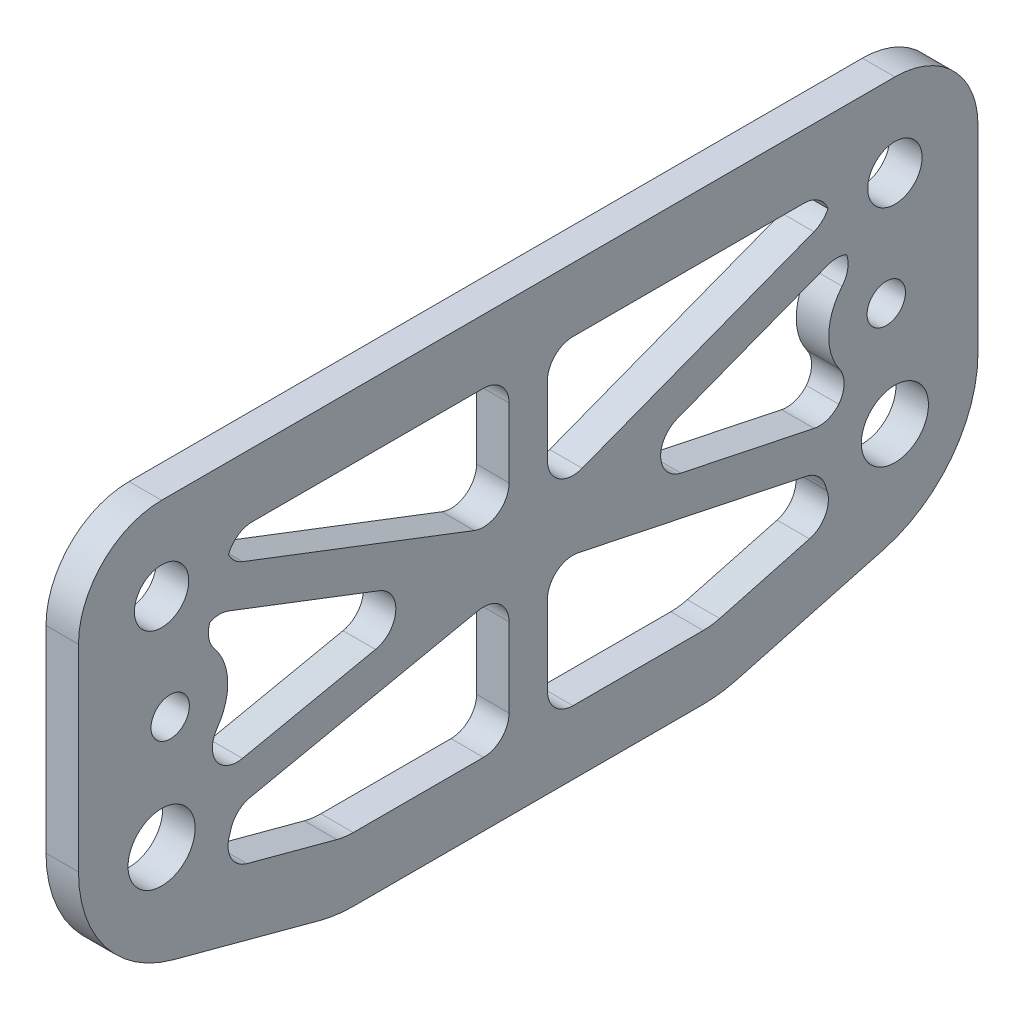
SolidWorks part; units mm, degrees
ref_plane "Front Plane" through (0, 0, 0) normal (0, 0, 1) x (1, 0, 0)
ref_plane "Top Plane" through (0, 0, 0) normal (0, 1, 0) x (1, 0, 0)
ref_plane "Right Plane" through (0, 0, 0) normal (1, 0, 0) x (0, 0, -1)
sketch "Sketch1" plane through (0, 0, 0) normal (1, 0, 0) x (0, 0, -1)
  line L0 (15, 17.5) -> (28.675, 17.5)
  line L1 (-15, -17.5) -> (15, -17.5)
  line L3 (-15, 17.5) -> (15, 17.5)
  line L5 (-15, -17.5) -> (15, 17.5) construction
  line L6 (-15, 17.5) -> (15, -17.5) construction
  line L8 (0, 17.5) -> (0, -17.5) construction
  line L10 (-15, 17.5) -> (-28.675, 17.5)
  line L11 (23.175, 120.4881) -> (23.175, -106.9119) construction
  line L13 (35.175, 11) -> (35.175, -4.4209)
  line L14 (27.7632, -14.0801) -> (15, -17.5)
  line L16 (-35.175, 11) -> (-35.175, -4.4209)
  line L17 (-27.7632, -14.0801) -> (-15, -17.5)
  arc A0 (28.675, 17.5) -> (35.175, 11) centre (28.675, 11) cw
  circle A1 centre (28.675, 11) radius 5.5 construction
  circle A2 centre (-28.675, 11) radius 5.5 construction
  arc A3 (-28.675, 17.5) -> (-35.175, 11) centre (-28.675, 11) ccw
  arc A4 (35.175, -4.4209) -> (27.7632, -14.0801) centre (25.175, -4.4209) cw
  circle A5 centre (28.675, 11) radius 2.125
  arc A6 (-35.175, -4.4209) -> (-27.7632, -14.0801) centre (-25.175, -4.4209) ccw
  circle A9 centre (-28.675, 11) radius 2.125
  circle A11 centre (28, 2.5) radius 1.5
  circle A12 centre (-28, 2.5) radius 1.5
  circle A13 centre (28.675, -6) radius 5.5 construction
  circle A14 centre (28.675, -6) radius 2.625
  circle A15 centre (-28.675, -6) radius 2.625
  circle A16 centre (-28.675, -6) radius 5.5 construction
  point P0 (0, 0)
  point P28 (0, 0)
  point P32 (28.2464, -10.5335)
  point P33 (28.2464, -11.8016)
  point P36 (0, 0)
  point P37 (0, 0)
  point P38 (26.8628, -12.5)
  point P39 (0, 0)
  point P40 (28.2464, -13.9573)
  point P41 (0, 0)
  point P42 (0, 0)
  point P43 (28.2464, -6.5205)
  point P44 (28.675, -5.4108)
  point P45 (28.675, -5.3598)
  dimension "D1" = 11
  dimension "D2" = 1
  dimension "D3" = 4.25
  dimension "D4" = 3
  dimension "D6" = 15
  dimension "D8" = 10
  dimension "D11" = 5.25
  dimension "D12" = 11
  dimension "D5" = 35
  dimension "D7" = 30
  dimension "D9" = 28
  dimension "D10" = 8.5
  dimension "D13" = 8.5
extrude "Boss-Extrude1" add sketch "Sketch1" along normal blind 2.54
fillet "Fillet1" radius 10 2 edges at (1.27, -17.5, -15) (1.27, -17.5, 15)
sketch "Sketch2" plane through (0, 0, 0) normal (1, 0, 0) x (0, 0, -1)
  line L0 (-28.675, 11) -> (0, 0)
  line L5 (0, 12.5) -> (0, -12.5) construction
  line L7 (-28, 2.5) -> (0, 0)
  line L8 (0, 17.5) -> (0, -17.5) construction
  line L9 (-28.675, -6) -> (0, 0)
  line L10 (-28.9822, -4.5318) -> (-0.3072, 1.4682)
  line L11 (-28.3678, -7.4682) -> (0.3072, -1.4682)
  line L16 (-13.6835, -12.5) -> (13.6835, -12.5)
  line L17 (14.9776, -12.3296) -> (26.4691, -9.2505)
  line L18 (30.175, -4.4209) -> (30.175, 11)
  line L19 (28.675, 12.5) -> (-28.675, 12.5)
  line L20 (-30.175, 11) -> (-30.175, -4.4209)
  line L21 (-26.4691, -9.2505) -> (-14.9776, -12.3296)
  line L22 (-13.6835, -12.5) -> (13.6835, -12.5)
  line L23 (14.9776, -12.3296) -> (26.4691, -9.2505)
  line L24 (30.175, -4.4209) -> (30.175, 11)
  line L25 (28.675, 12.5) -> (-28.675, 12.5)
  line L26 (-30.175, 11) -> (-30.175, -4.4209)
  line L27 (-26.4691, -9.2505) -> (-14.9776, -12.3296)
  line L32 (0, -12.5) -> (0, 12.5) construction
  line L33 (0, 0) -> (0, -12.5)
  line L34 (-1.5, 12.5) -> (-1.5, -12.5)
  line L35 (1.5, 12.5) -> (1.5, -12.5)
  line L36 (-1.5, 12.5) -> (1.5, 12.5)
  line L37 (-1.5, -12.5) -> (1.5, -12.5)
  line L38 (-29.2122, 9.5995) -> (-0.5372, -1.4005)
  line L39 (-28.1378, 12.4005) -> (0.5372, 1.4005)
  line L40 (28.675, -6) -> (0, 0)
  line L41 (28.3678, -7.4682) -> (-0.3072, -1.4682)
  line L42 (28.1378, 12.4005) -> (-0.5372, 1.4005)
  line L43 (28.9822, -4.5318) -> (0.3072, 1.4682)
  line L44 (29.2122, 9.5995) -> (0.5372, -1.4005)
  line L45 (28.675, 11) -> (0, 0)
  arc A0 (-34.8843, -3.8991) -> (-35.5003, -6.8306) centre (-35.1121, -5.3817) ccw
  circle A2 centre (-28, 2.5) radius 4.5
  circle A3 centre (-28, 2.5) radius 4.5
  circle A5 centre (28, 2.5) radius 4.5
  circle A6 centre (28, 2.5) radius 4.5
  circle A10 centre (28.675, -6) radius 5.625
  circle A11 centre (-28.675, 11) radius 5.125
  arc A12 (13.6835, -12.5) -> (14.9776, -12.3296) centre (13.6835, -7.5) ccw
  arc A13 (26.4691, -9.2505) -> (30.175, -4.4209) centre (25.175, -4.4209) ccw
  arc A14 (30.175, 11) -> (28.675, 12.5) centre (28.675, 11) ccw
  arc A15 (-28.675, 12.5) -> (-30.175, 11) centre (-28.675, 11) ccw
  arc A16 (-30.175, -4.4209) -> (-26.4691, -9.2505) centre (-25.175, -4.4209) ccw
  arc A17 (-14.9776, -12.3296) -> (-13.6835, -12.5) centre (-13.6835, -7.5) ccw
  arc A18 (13.6835, -12.5) -> (14.9776, -12.3296) centre (13.6835, -7.5) ccw
  arc A19 (26.4691, -9.2505) -> (30.175, -4.4209) centre (25.175, -4.4209) ccw
  arc A20 (30.175, 11) -> (28.675, 12.5) centre (28.675, 11) ccw
  arc A21 (-28.675, 12.5) -> (-30.175, 11) centre (-28.675, 11) ccw
  arc A22 (-30.175, -4.4209) -> (-26.4691, -9.2505) centre (-25.175, -4.4209) ccw
  arc A23 (-14.9776, -12.3296) -> (-13.6835, -12.5) centre (-13.6835, -7.5) ccw
  circle A24 centre (-28.675, 11) radius 5.125
  circle A25 centre (28.675, -6) radius 5.625
  circle A26 centre (28.675, 11) radius 5.125
  circle A27 centre (28.675, 11) radius 5.125
  circle A31 centre (-28.675, -6) radius 5.625
  circle A32 centre (-28.675, -6) radius 5.625
  dimension "D10" = 1.5
  dimension "D11" = 3
  dimension "D2" = 1.5
  dimension "D1" = 5
  dimension "D3" = 3
  dimension "D4" = 3
  dimension "D5" = 3
  dimension "D6" = 3
  dimension "D7" = 1.5
  dimension "D8" = 1.5
  dimension "D9" = 1.5
  dimension "D13" = 1.5
  dimension "D14" = 1.5
  dimension "D15" = 3
extrude "Cut-Extrude2" cut sketch "Sketch2" along normal through all contours A25 L41 L35 L22 A18 L23 | A32 L27 A23 L22 L34 L11 | A27 L44 L43 A25 A6 | A24 A3 L7 L38 | A32 L10 L38 L7 A3 | A24 L39 L34 L25 | A27 L25 L35 L42 region at (0, 3.6011, 18.1308) region at (0, 8.9687, 9.9837) region at (0, -0.3466, 17.9186) region at (0, 8.9687, -9.9837) region at (0, -8.0015, 10.9326) region at (0, -8.0015, -10.9326) region at (0, 1.5935, -18.0229)
fillet "Fillet2" radius 2 26 edges at (1.27, -12.5, -1.5) (1.27, -12.5, 1.5) (1.27, 6.5746, -26.0901) (1.27, 6.5746, 26.0901) (1.27, -1.8463, -1.5) (1.27, -9.7764, -24.5062) (1.27, -6.3579, -23.0614) (1.27, 12.5, -1.5) (1.27, 2.182, -1.5) (1.27, 10.6453, -23.5623) (1.27, 12.5, -23.7744) (1.27, -6.3579, 23.0614) (1.27, -9.7764, 24.5062) (1.27, 0.4246, -5.2949) (1.27, -3.4215, -23.6758) (1.27, -1.2984, -25.5871) (1.27, 7.8443, -24.6368) (1.27, -1.2984, 25.5871) (1.27, -3.4215, 23.6758) (1.27, 0.4246, 5.2949) (1.27, 7.8443, 24.6368) (1.27, -1.8463, 1.5) (1.27, 12.5, 1.5) (1.27, 12.5, 23.7744) (1.27, 10.6453, 23.5623) (1.27, 2.182, 1.5)
